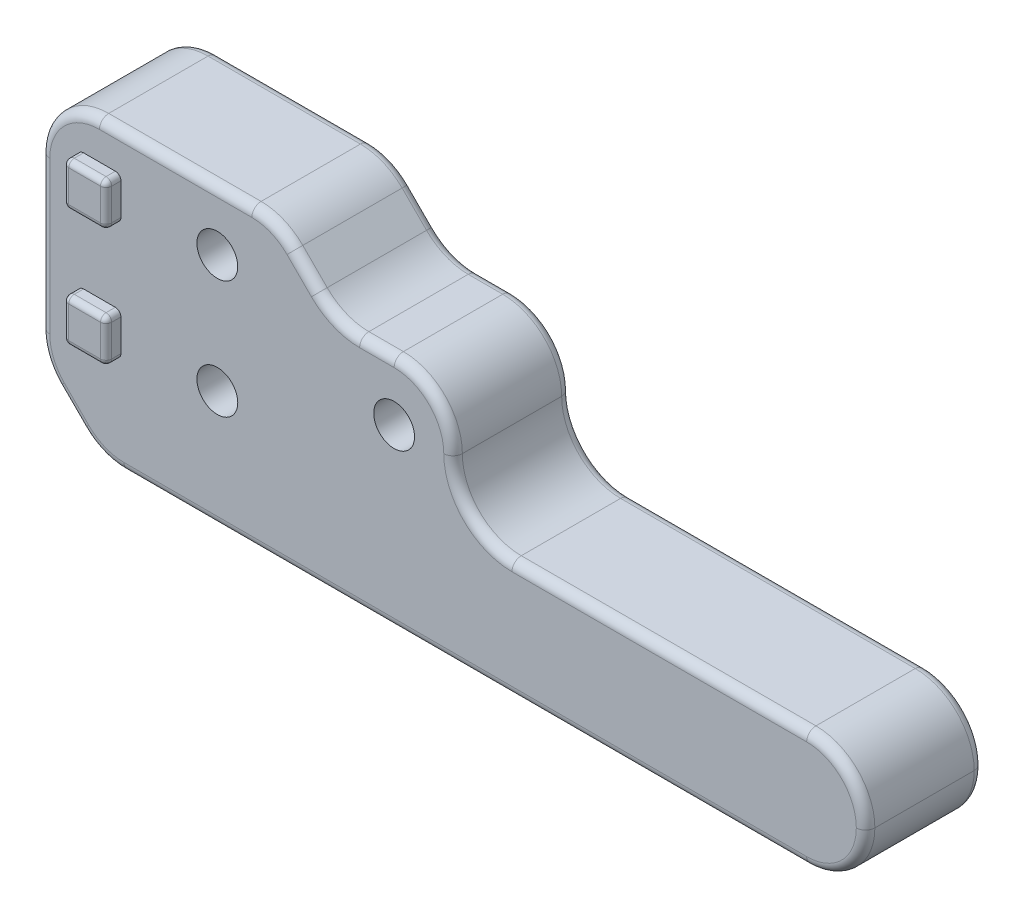
SolidWorks part; units mm, degrees
ref_plane "Front Plane" through (0, 0, 0) normal (0, 0, 1) x (1, 0, 0)
ref_plane "Top Plane" through (0, 0, 0) normal (0, 1, 0) x (1, 0, 0)
ref_plane "Right Plane" through (0, 0, 0) normal (1, 0, 0) x (0, 0, -1)
sketch "Sketch1" plane through (0, 0, 0) normal (0, 0, 1) x (1, 0, 0)
  line L0 (0, -12.7) -> (25.4, -12.7) construction
  line L1 (0, 0) -> (25.4, 0)
  line L2 (0, 0) -> (0, -25.4)
  line L3 (0, -25.4) -> (25.4, -25.4)
  line L4 (25.4, 0) -> (25.4, -25.4)
  line L5 (25.4, 0) -> (31.75, -6.35)
  line L6 (31.75, -6.35) -> (44.45, -6.35)
  line L7 (44.45, -6.35) -> (44.45, -19.05)
  line L8 (44.45, -19.05) -> (76.2, -19.05)
  line L9 (76.2, -19.05) -> (76.2, -31.75)
  line L10 (76.2, -31.75) -> (6.35, -31.75)
  line L11 (6.35, -31.75) -> (0, -25.4)
  line L13 (76.2, -19.05) -> (88.9, -19.05)
  line L14 (76.2, -19.05) -> (76.2, -31.75)
  line L15 (76.2, -31.75) -> (88.9, -31.75)
  line L16 (88.9, -19.05) -> (88.9, -31.75)
  line L17 (4.0386, -4.0386) -> (8.6614, -4.0386)
  line L18 (4.0386, -4.0386) -> (4.0386, -8.6614)
  line L19 (4.0386, -8.6614) -> (8.6614, -8.6614)
  line L20 (8.6614, -4.0386) -> (8.6614, -8.6614)
  line L21 (4.0386, -4.0386) -> (8.6614, -8.6614) construction
  line L22 (4.0386, -8.6614) -> (8.6614, -4.0386) construction
  line L23 (4.0386, -16.7386) -> (8.6614, -16.7386)
  line L24 (4.0386, -16.7386) -> (4.0386, -21.3614)
  line L25 (4.0386, -21.3614) -> (8.6614, -21.3614)
  line L26 (8.6614, -16.7386) -> (8.6614, -21.3614)
  line L27 (4.0386, -16.7386) -> (8.6614, -21.3614) construction
  line L28 (4.0386, -21.3614) -> (8.6614, -16.7386) construction
  circle A0 centre (19.05, -6.35) radius 2.2
  circle A1 centre (19.05, -19.05) radius 2.2
  circle A2 centre (38.1, -12.7) radius 2.2
  point P6 (0, -12.7)
  point P22 (6.35, -6.35)
  point P27 (6.35, -19.05)
  dimension "D11" = 4.4
  dimension "D1" = 25.4
  dimension "D2" = 25.4
  dimension "D3" = 6.35
  dimension "D4" = 45
  dimension "D5" = 12.7
  dimension "D6" = 6.35
  dimension "D7" = 45
  dimension "D8" = 12.7
  dimension "D9" = 76.2
  dimension "D10" = 12.7
  dimension "D12" = 6.35
  dimension "D13" = 6.35
  dimension "D14" = 4.6228
  dimension "D15" = 6.35
extrude "Boss-Extrude1" add sketch "Sketch1" along normal blind 12.7 contours L11 L10 L9 L8 L7 L6 L5 L4 L3 A2 | L4 L1 L2 L3 A1 A0 L17 L20 L19 L18 L23 L26 L25 L24 | L26 L23 L24 L25 | L20 L17 L18 L19 | L16 L13 L9 L15 region at (12.8369, -12.7, 0) region at (41.8174, -22.613, 0) region at (82.55, -25.4, 0) region at (6.35, -6.35, 0) region at (6.35, -19.05, 0)
extrude "Boss-Extrude2" add sketch "Sketch1<3>" along normal blind 1.6 from surface contours L20 L17 L18 L19 | L26 L23 L24 L25 region at (6.35, -6.35, 0) region at (6.35, -19.05, 0) starting at face at (40.3, -12.7, 12.7)
sketch "Sketch1<3>" plane through (0, 0, 0) normal (0, 0, 1) x (1, 0, 0) same geometry as "Sketch1"
fillet "Fillet1" radius 6.35 9 edges at (88.9, -31.75, 6.35) (88.9, -19.05, 6.35) (44.45, -19.05, 6.35) (44.45, -6.35, 6.35) (31.75, -6.35, 6.35) (25.4, 0, 6.35) (6.35, -31.75, 6.35) (0, -25.4, 6.35) (0, 0, 6.35)
fillet "Fillet2" radius 0.6 16 edges at (4.0386, -6.35, 14.3) (6.35, -4.0386, 14.3) (8.6614, -6.35, 14.3) (6.35, -8.6614, 14.3) (4.0386, -19.05, 14.3) (6.35, -16.7386, 14.3) (8.6614, -19.05, 14.3) (6.35, -21.3614, 14.3) (4.0386, -16.7386, 13.5) (8.6614, -16.7386, 13.5) (8.6614, -21.3614, 13.5) (4.0386, -21.3614, 13.5) (4.0386, -8.6614, 13.5) (8.6614, -8.6614, 13.5) (8.6614, -4.0386, 13.5) (4.0386, -4.0386, 13.5)
fillet "Fillet3" radius 1 32 edges at (1.8599, -1.8599, 0) (0, -14.5599, 0) (0.4834, -25.1998, 0) (3.175, -28.575, 0) (6.5502, -31.2666, 0) (45.7651, -31.75, 0) (87.0401, -29.8901, 0) (87.0401, -20.9099, 0) (66.675, -19.05, 0) (46.3099, -17.1901, 0) (42.5901, -8.2099, 0) (36.2401, -6.35, 0) (31.9502, -5.8666, 0) (28.575, -3.175, 0) (25.1998, -0.4834, 0) (46.3099, -17.1901, 12.7) (42.5901, -8.2099, 12.7) (36.2401, -6.35, 12.7) (31.9502, -5.8666, 12.7) (28.575, -3.175, 12.7) (25.1998, -0.4834, 12.7) (14.5599, 0, 12.7) (1.8599, -1.8599, 12.7) (0, -14.5599, 12.7) (0.4834, -25.1998, 12.7) (3.175, -28.575, 12.7) (6.5502, -31.2666, 12.7) (45.7651, -31.75, 12.7) (87.0401, -29.8901, 12.7) (87.0401, -20.9099, 12.7) (14.5599, 0, 0) (66.675, -19.05, 12.7)
